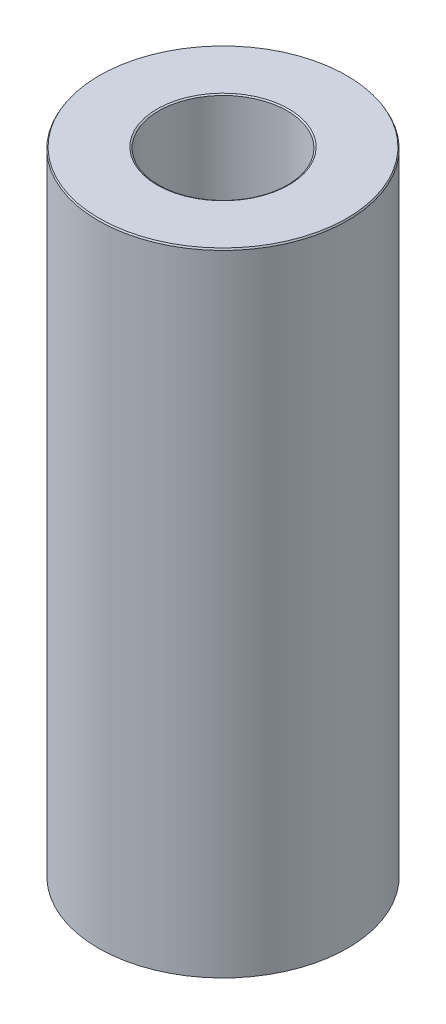
SolidWorks part; units mm, degrees
ref_plane "Front Plane" through (0, 0, 0) normal (0, 0, 1) x (1, 0, 0)
ref_plane "Top Plane" through (0, 0, 0) normal (0, 1, 0) x (1, 0, 0)
ref_plane "Right Plane" through (0, 0, 0) normal (1, 0, 0) x (0, 0, -1)
sketch "Sketch1" plane through (0, 0, 0) normal (0, 1, 0) x (1, 0, 0)
  circle A0 centre (0, 0) radius 35
  dimension "SLEEVE_OD" = 70
extrude "Boss-Extrude1" add sketch "Sketch1" along normal blind 177.648
sketch "Sketch2" plane through (0, 0, 0) normal (0, 1, 0) x (1, 0, 0)
  circle A0 centre (0, 0) radius 18.0758
  dimension "BORE_D" = 36.1515
extrude "Cut-Extrude1" cut sketch "Sketch2" along normal through all
chamfer "Chamfer1" distance 0.4301 angle 30 4 edges at (0, 177.648, 18.0758) (0, 0, 18.0758) (0, 0, 35) (0, 177.648, 35) first distance on face at (0, 177.648, 18.0758) first distance on face at (0, 0, 18.0758) first distance on face at (0, 177.648, 35)
